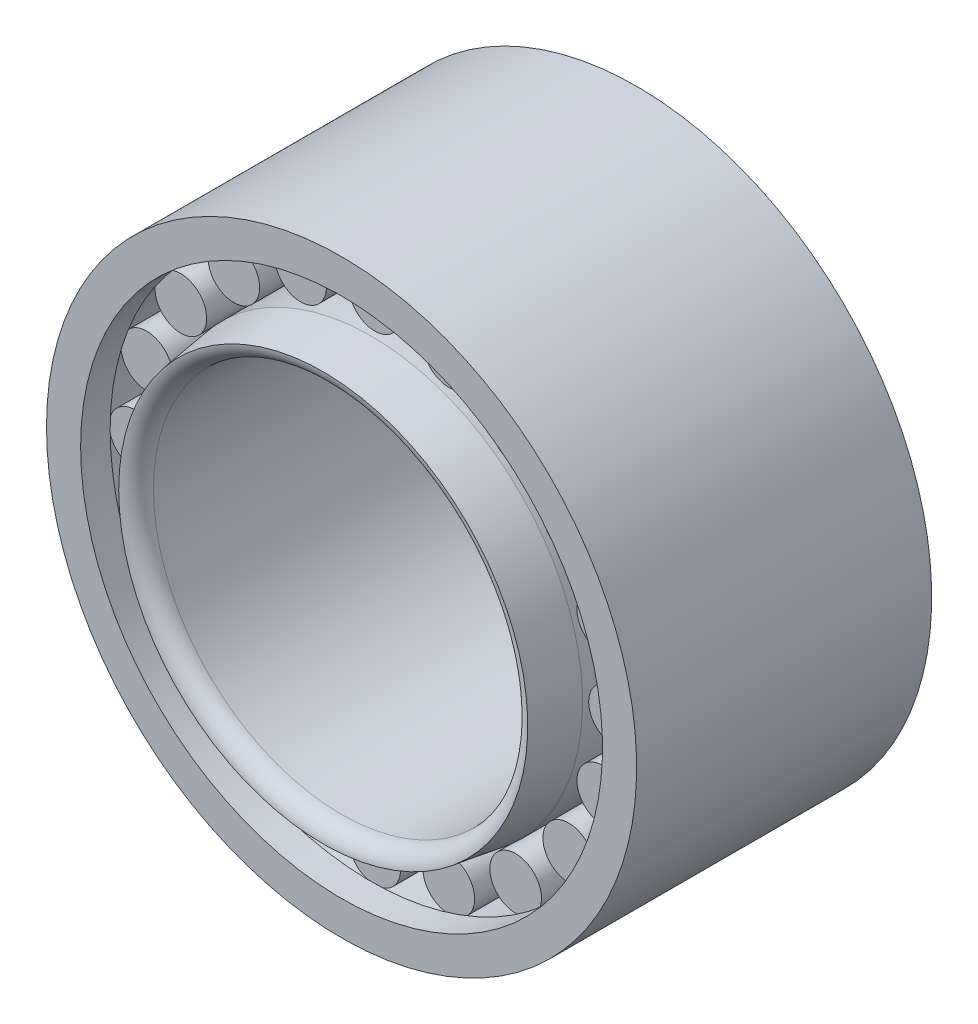
SolidWorks part; units mm, degrees
ref_plane "Front Plane" through (0, 0, 0) normal (0, 0, 1) x (1, 0, 0)
ref_plane "Top Plane" through (0, 0, 0) normal (0, 1, 0) x (1, 0, 0)
ref_plane "Right Plane" through (0, 0, 0) normal (1, 0, 0) x (0, 0, -1)
sketch "Sketch1" plane through (0, 0, 0) normal (1, 0, 0) x (0, 0, -1)
  line L0 (-8, 14.15) -> (-8, 16)
  line L1 (-8, 16) -> (8, 16)
  line L2 (8, 16) -> (8, 14.15)
  line L3 (8, 14.15) -> (6.4, 14.15)
  line L4 (6.4, 14.15) -> (6.4, 14.53)
  line L5 (6.4, 14.53) -> (-6.4, 14.53)
  line L6 (-6.4, 14.53) -> (-6.4, 14.15)
  line L7 (-6.4, 14.15) -> (-8, 14.15)
  point P7 (0, 14.53)
  dimension "D1" = 16
  dimension "D2" = 14.53
  dimension "D3" = 14.15
  dimension "D4" = 1.6
  dimension "D5" = 16
ref_axis "Axis1" through (0, 0, -22) along (0, 0, 1)
revolve "Revolve1" add sketch "Sketch1" angle 360 about axis through (0, 0, -22) along (0, 0, 1)
sketch "Sketch2" plane through (0, 0, 0) normal (1, 0, 0) x (0, 0, -1)
  line L0 (8, 10.2) -> (-8, 10.2)
  line L1 (-9, 11.09) -> (-6.4, 11.47)
  line L2 (-6.4, 11.47) -> (6.4, 11.47)
  line L3 (6.4, 11.47) -> (9, 11.09)
  line L4 (9, 11.09) -> (9, 11.2)
  line L5 (-9, 11.09) -> (-9, 11.2)
  line L6 (22, 0) -> (-22, 0) construction
  arc A0 (8, 10.2) -> (9, 11.2) centre (8, 11.2) ccw
  arc A1 (-8, 10.2) -> (-9, 11.2) centre (-8, 11.2) cw
  point P5 (16, 10.1525)
  point P13 (0, 10.2)
  point P15 (0, 11.47)
  dimension "D1" = 1
  dimension "D4" = 10.2
  dimension "D2" = 16
  dimension "D3" = 11.47
  dimension "D5" = 12.8
  dimension "D6" = 11.09
revolve "Revolve2" add sketch "Sketch2" angle 360 about axis through (0, 0, -22) along (0, 0, 1) region at (0, 10.8198, 0)
sketch "Sketch3" plane through (0, 0, 0) normal (1, 0, 0) x (0, 0, -1)
  line L0 (-6.2, 13) -> (-6.2, 14.4)
  line L1 (-6.2, 14.4) -> (6.2, 14.4)
  line L2 (6.2, 14.4) -> (6.2, 13)
  line L3 (6.2, 13) -> (-6.2, 13)
  line L4 (22, 0) -> (-22, 0) construction
  point P4 (0, 13)
  dimension "D1" = 12.4
  dimension "D2" = 1.4
  dimension "D3" = 13
revolve "Revolve3" add sketch "Sketch3" angle 360 about L3
pattern_circular "CirPattern1" count 20 over 360 about axis through (0, 0, -22) along (0, 0, -1) of bodies 103
